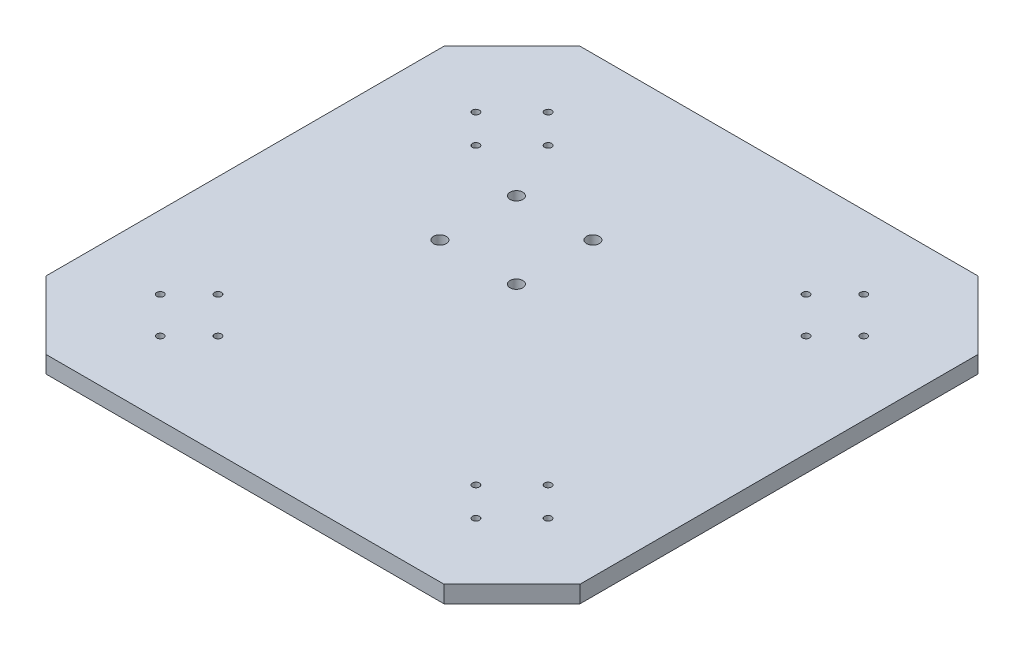
SolidWorks part; units mm, degrees
material "Titanium Ti-8Mn, Annealed"
ref_plane "Front Plane" through (0, 0, 0) normal (0, 0, 1) x (1, 0, 0)
ref_plane "Top Plane" through (0, 0, 0) normal (0, 1, 0) x (1, 0, 0)
ref_plane "Right Plane" through (0, 0, 0) normal (1, 0, 0) x (0, 0, -1)
sketch "Sketch1" plane through (0, 0, 0) normal (0, 1, 0) x (1, 0, 0)
  line L5 (-96.7157, 125) -> (-125, 96.7157)
  line L6 (-125, 125) -> (125, 125) construction
  line L22 (-125, 125) -> (-125, -125) construction
  line L23 (-125, -125) -> (125, -125) construction
  line L24 (125, 125) -> (125, -125) construction
  line L25 (-125, 125) -> (125, -125) construction
  line L26 (-125, -125) -> (125, 125) construction
  line L27 (125, 96.7157) -> (96.7157, 125)
  line L28 (96.7157, -125) -> (125, -96.7157)
  line L29 (-125, -96.7157) -> (-96.7157, -125)
  line L30 (-96.7157, 125) -> (96.7157, 125)
  line L31 (125, 96.7157) -> (125, -96.7157)
  line L32 (-96.7157, -125) -> (96.7157, -125)
  line L33 (-125, 96.7157) -> (-125, -96.7157)
  point P0 (0, 0)
  point P17 (0, 0)
  dimension "D1" = 40
  dimension "D2" = 250
  dimension "D3" = 250
extrude "Boss-Extrude1" add sketch "Sketch1" along normal blind 10
sketch "Sketch2" plane through (0, 10, 0) normal (0, 1, 0) x (1, 0, 0)
  line L0 (-110.8579, -110.8579) -> (110.8579, 110.8579) construction
  line L1 (-125, -96.7157) -> (-96.7157, -125) construction
  line L2 (125, 96.7157) -> (96.7157, 125) construction
  line L3 (-110.8579, 110.8579) -> (110.8579, -110.8579) construction
  line L4 (-96.7157, 125) -> (-125, 96.7157) construction
  line L5 (96.7157, -125) -> (125, -96.7157) construction
  circle A0 centre (-97.0693, -75.8561) radius 2.05
  circle A1 centre (-114.0398, -92.8266) radius 2.05
  circle A2 centre (-75.8561, -97.0693) radius 2.05
  circle A3 centre (-92.8266, -114.0398) radius 2.05
  circle A4 centre (-75.8561, 97.0693) radius 2.05
  circle A5 centre (-92.8266, 114.0398) radius 2.05
  circle A6 centre (-114.0398, 92.8266) radius 2.05
  circle A7 centre (-97.0693, 75.8561) radius 2.05
  circle A8 centre (97.0693, 75.8561) radius 2.05
  circle A9 centre (114.0398, 92.8266) radius 2.05
  circle A10 centre (92.8266, 114.0398) radius 2.05
  circle A11 centre (75.8561, 97.0693) radius 2.05
  circle A12 centre (75.8561, -97.0693) radius 2.05
  circle A13 centre (92.8266, -114.0398) radius 2.05
  circle A14 centre (114.0398, -92.8266) radius 2.05
  circle A15 centre (97.0693, -75.8561) radius 2.05
  point P47 (0, 0)
  dimension "D5" = 4.1
  dimension "D6" = 4.1
  dimension "D1" = 15
  dimension "D2" = 15
  dimension "D3" = 24
  dimension "D4" = 10.5
extrude "Cut-Extrude1" cut sketch "Sketch2" against normal up to next
sketch "Sketch3" plane through (0, 10, 0) normal (0, 1, 0) x (1, 0, 0)
  line L0 (-125, 96.7157) -> (-125, -96.7157) construction
  line L1 (-157, 157) -> (157, 157) construction
  line L2 (-157, 157) -> (-157, -157) construction
  line L3 (-157, -157) -> (157, -157) construction
  line L4 (157, 157) -> (157, -157) construction
  line L5 (-157, 157) -> (157, -157) construction
  line L6 (-157, -157) -> (157, 157) construction
  line L7 (96.7157, 125) -> (-96.7157, 125) construction
  line L8 (-125, 96.7157) -> (-157, 64.7157)
  line L9 (-157, 64.7157) -> (-157, -64.7157)
  line L10 (-157, -64.7157) -> (-125, -96.7157)
  line L11 (-125, -96.7157) -> (-96.7157, -125) construction
  line L12 (-96.7157, 125) -> (-125, 96.7157) construction
  line L13 (-125, 96.7157) -> (-125, -96.7157)
  line L14 (64.7157, 157) -> (-64.7157, 157)
  line L15 (96.7157, 125) -> (64.7157, 157)
  line L16 (96.7157, 125) -> (-96.7157, 125)
  line L17 (-64.7157, 157) -> (-96.7157, 125)
  line L18 (157, -64.7157) -> (157, 64.7157)
  line L19 (125, -96.7157) -> (157, -64.7157)
  line L20 (125, -96.7157) -> (125, 96.7157)
  line L21 (157, 64.7157) -> (125, 96.7157)
  line L22 (-64.7157, -157) -> (64.7157, -157)
  line L23 (-96.7157, -125) -> (-64.7157, -157)
  line L24 (-96.7157, -125) -> (96.7157, -125)
  line L25 (64.7157, -157) -> (96.7157, -125)
  point P0 (0, 0)
  point P35 (0, 0)
  dimension "D1" = 32
  dimension "D2" = 32
extrude "Boss-Extrude2" add sketch "Sketch3" against normal up to surface (10 mm away) up to face at (-92.8266, 0, -116.0898)
sketch "Sketch4" plane through (0, 10, 0) normal (0, 1, 0) x (1, 0, 0)
  line L0 (-64.7157, 157) -> (-157, 64.7157) construction
  line L1 (-135.049, 138.9926) -> (135.049, 138.9926) construction
  line L2 (-135.049, 138.9926) -> (-135.049, -138.9926) construction
  line L3 (-135.049, -138.9926) -> (135.049, -138.9926) construction
  line L4 (135.049, 138.9926) -> (135.049, -138.9926) construction
  line L5 (-135.049, 138.9926) -> (135.049, -138.9926) construction
  line L6 (-135.049, -138.9926) -> (135.049, 138.9926) construction
  line L7 (-157, 64.7157) -> (-64.7157, 157)
  line L8 (64.7157, 157) -> (157, 64.7157)
  line L9 (-157, 64.7157) -> (-157, 117.0416)
  line L10 (-157, 117.0416) -> (-117.0416, 157)
  line L11 (-117.0416, 157) -> (-64.7157, 157)
  line L12 (64.7157, 157) -> (-64.7157, 157) construction
  line L13 (64.7157, 157) -> (117.0416, 157)
  line L14 (117.0416, 157) -> (157, 117.0416)
  line L15 (157, 117.0416) -> (157, 64.7157)
  line L16 (157, -64.7157) -> (64.7157, -157)
  line L17 (157, -64.7157) -> (157, -117.0416)
  line L18 (157, -117.0416) -> (117.0416, -157)
  line L19 (117.0416, -157) -> (64.7157, -157)
  line L20 (-64.7157, -157) -> (-157, -64.7157)
  line L21 (-64.7157, -157) -> (-117.0416, -157)
  line L22 (-117.0416, -157) -> (-157, -117.0416)
  line L23 (-157, -117.0416) -> (-157, -64.7157)
  point P0 (0, 0)
  point P31 (0, 0)
  dimension "D1" = 37
  dimension "D2" = 277.9853
extrude "Boss-Extrude3" add sketch "Sketch4" against normal up to surface (10 mm away) up to face at (-92.8266, 0, -116.0898)
sketch "Sketch5" plane through (0, 0, 0) normal (0, -1, 0) x (1, 0, 0)
  circle A0 centre (-114.0398, 92.8266) radius 3.5
  circle A1 centre (-92.8266, 114.0398) radius 3.5
  circle A2 centre (-75.8561, 97.0693) radius 3.5
  circle A3 centre (-97.0693, 75.8561) radius 3.5
  circle A4 centre (114.0398, 92.8266) radius 3.5
  circle A5 centre (92.8266, 114.0398) radius 3.5
  circle A6 centre (75.8561, 97.0693) radius 3.5
  circle A7 centre (97.0693, 75.8561) radius 3.5
  circle A8 centre (92.8266, -114.0398) radius 3.5
  circle A9 centre (114.0398, -92.8266) radius 3.5
  circle A10 centre (97.0693, -75.8561) radius 3.5
  circle A11 centre (75.8561, -97.0693) radius 3.5
  circle A12 centre (-114.0398, -92.8266) radius 3.5
  circle A13 centre (-92.8266, -114.0398) radius 3.5
  circle A14 centre (-75.8561, -97.0693) radius 3.5
  circle A15 centre (-97.0693, -75.8561) radius 3.5
  point P39 (0, 0)
  dimension "D1" = 7
extrude "Cut-Extrude2" cut sketch "Sketch5" against normal blind 4
sketch "Sketch6" plane through (0, 0, 0) normal (0, -1, 0) x (1, 0, 0)
  line L0 (-137, -39.6) -> (177, -39.6) construction
  line L1 (-157, -117.0416) -> (-157, 117.0416) construction
  line L8 (-47, -29.6) -> (-27, -49.6) construction
  line L9 (-47, -49.6) -> (-27, -29.6) construction
  line L17 (-59.5, -17.1) -> (-14.5, -62.1) construction
  line L18 (-59.5, -62.1) -> (-14.5, -17.1) construction
  circle A0 centre (-59.5, -17.1) radius 3.75
  circle A1 centre (-14.5, -17.1) radius 3.75
  circle A2 centre (-14.5, -62.1) radius 3.75
  circle A3 centre (-59.5, -62.1) radius 3.75
  point P4 (-37, -39.6)
  point P6 (-37, -39.6)
  dimension "D8" = 7.5
  dimension "D1" = 20
  dimension "D2" = 20
  dimension "D3" = 120
  dimension "D5" = 39.6
  dimension "D6" = 45
  dimension "D7" = 45
  dimension "D9" = 4
extrude "Cut-Extrude4" cut sketch "Sketch6" against normal through all
